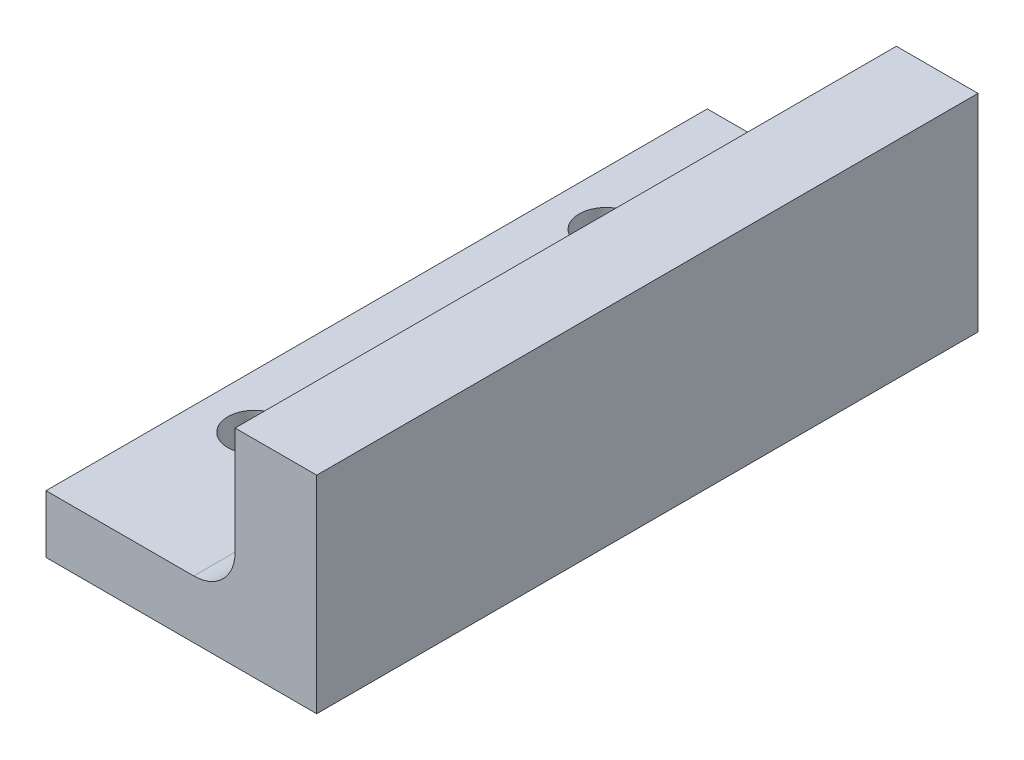
SolidWorks part; units mm, degrees
material "2024 Alloy (SN)"
ref_plane "Front Plane" through (0, 0, 0) normal (0, 0, 1) x (1, 0, 0)
ref_plane "Top Plane" through (0, 0, 0) normal (0, 1, 0) x (1, 0, 0)
ref_plane "Right Plane" through (0, 0, 0) normal (1, 0, 0) x (0, 0, -1)
sketch "Sketch1" plane through (0, 0, 0) normal (0, 1, 0) x (1, 0, 0)
  line L1 (2.6, 16) -> (-2.6, 16)
  line L2 (2.6, 16) -> (2.6, -16)
  line L3 (2.6, -16) -> (-2.6, -16)
  line L4 (-2.6, 16) -> (-2.6, -16)
  line L5 (2.6, 16) -> (-2.6, -16) construction
  line L6 (2.6, -16) -> (-2.6, 16) construction
  circle A0 centre (0, -8.5) radius 1.3
  circle A2 centre (0, 8.5) radius 1.3
  point P0 (0, 0)
  dimension "D2" = 2.6
  dimension "D3" = 17
  dimension "D4" = 8.5
  dimension "D5" = 7.5
  dimension "D1" = 2.6
extrude "Boss-Extrude1" add sketch "Sketch1" along normal blind 2.8
sketch "Sketch2" plane through (2.6, 0, 0) normal (1, 0, 0) x (0, 0, -1)
  line L0 (16, 2.8) -> (16, 0) construction
  line L1 (-16, 0) -> (16, 0)
  line L2 (-16, 0) -> (-16, 10)
  line L3 (-16, 10) -> (16, 10)
  line L4 (16, 0) -> (16, 10)
  dimension "D1" = 10
extrude "Boss-Extrude2" add sketch "Sketch2" along normal blind 7.9
sketch "Sketch3" plane through (0, 10, 0) normal (0, 1, 0) x (1, 0, 0)
  line L0 (10.5, -16) -> (2.6, -16) construction
  line L1 (2.6, 16) -> (6.55, 16)
  line L2 (2.6, 16) -> (2.6, -16)
  line L3 (2.6, -16) -> (6.55, -16)
  line L4 (6.55, 16) -> (6.55, -16)
extrude "Cut-Extrude1" cut sketch "Sketch3" against normal up to surface (7.2 mm away) up to face at (0, 2.8, 0)
fillet "Fillet1" radius 2 1 edges at (6.55, 2.8, 0)
